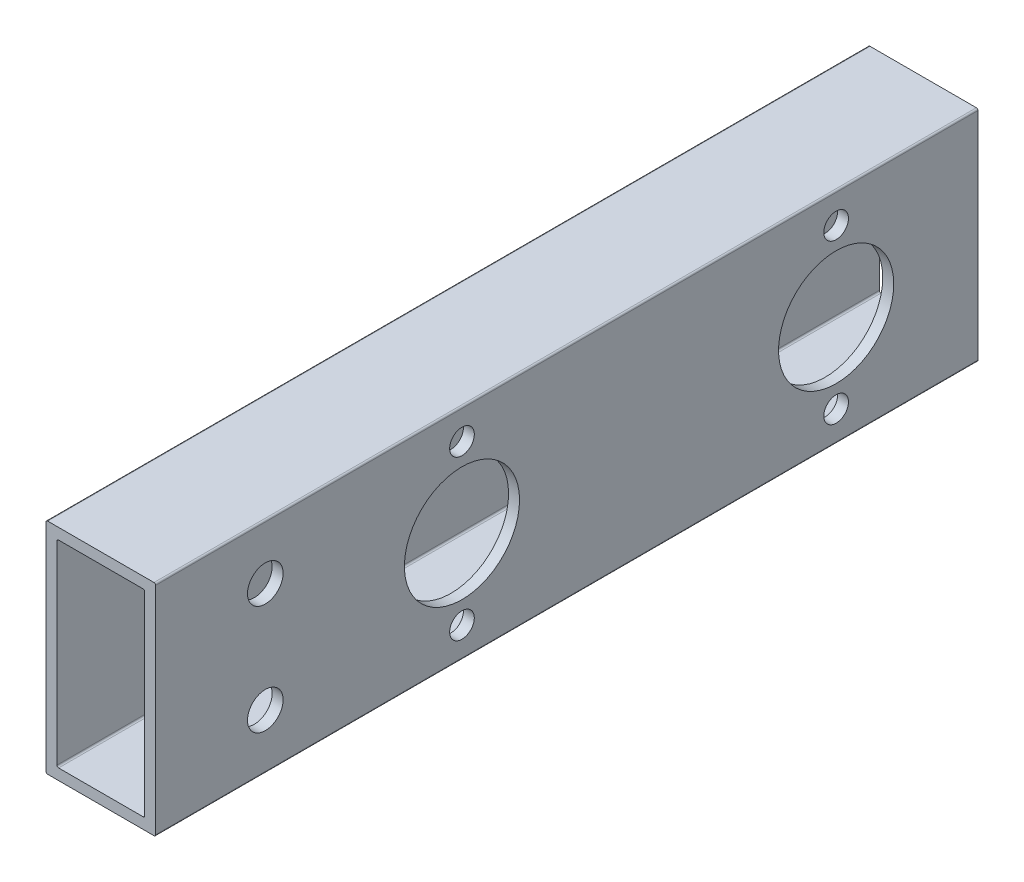
SolidWorks part; units mm, degrees
ref_plane "正面" through (0, 0, 0) normal (0, 0, 1) x (1, 0, 0)
ref_plane "平面" through (0, 0, 0) normal (0, 1, 0) x (1, 0, 0)
ref_plane "右側面" through (0, 0, 0) normal (1, 0, 0) x (0, 0, -1)
ref_plane "平面1" through (0, 0, 0) normal (0, 0, 1) x (1, 0, 0)
sketch "ｽｹｯﾁ1" plane through (0, 0, 0) normal (0, 0, 1) x (1, 0, 0)
  line L0 (0.3, 0) -> (19.7, 0)
  line L1 (20, 0.3) -> (20, 39.7)
  line L2 (19.7, 40) -> (0.3, 40)
  line L3 (0, 39.7) -> (0, 0.3)
  line L4 (2.3, 2) -> (17.7, 2)
  line L5 (18, 2.3) -> (18, 37.7)
  line L6 (17.7, 38) -> (2.3, 38)
  line L7 (2, 37.7) -> (2, 2.3)
  arc A0 (0, 0.3) -> (0.3, 0) centre (0.3, 0.3) ccw
  arc A1 (19.7, 0) -> (20, 0.3) centre (19.7, 0.3) ccw
  arc A2 (20, 39.7) -> (19.7, 40) centre (19.7, 39.7) ccw
  arc A3 (0.3, 40) -> (0, 39.7) centre (0.3, 39.7) ccw
  arc A4 (2, 2.3) -> (2.3, 2) centre (2.3, 2.3) ccw
  arc A5 (17.7, 2) -> (18, 2.3) centre (17.7, 2.3) ccw
  arc A6 (18, 37.7) -> (17.7, 38) centre (17.7, 37.7) ccw
  arc A7 (2.3, 38) -> (2, 37.7) centre (2.3, 37.7) ccw
extrude "ﾎﾞｽ - 押し出し1" add sketch "ｽｹｯﾁ1" against normal blind 150
sketch "ｽｹｯﾁ2" plane through (0, 0, 0) normal (-1, 0, 0) x (0, 0, 1)
  circle A0 centre (-20, 30) radius 3.25
  circle A1 centre (-20, 10) radius 3.25
extrude "ｶｯﾄ - 押し出し1" cut sketch "ｽｹｯﾁ2" against normal through all
sketch "ｽｹｯﾁ3" plane through (20, 0, 0) normal (1, 0, 0) x (0, 0, -1)
  line L0 (150, 20) -> (124.125, 20) construction
  line L1 (150, 0.3) -> (150, 39.7) construction
  circle A0 centre (124.125, 20) radius 10.5
  dimension "D1" = 21
extrude "ｶｯﾄ - 押し出し2" cut sketch "ｽｹｯﾁ3" against normal through all
sketch "ｽｹｯﾁ4" plane through (20, 0, 0) normal (1, 0, 0) x (0, 0, -1)
  line L0 (30, 20) -> (55.875, 20) construction
  line L1 (30, 38) -> (30, 2) construction
  circle A0 centre (55.875, 20) radius 10.5
  dimension "D1" = 21
extrude "ｶｯﾄ - 押し出し3" cut sketch "ｽｹｯﾁ4" against normal through all
sketch "ｽｹｯﾁ5" plane through (20, 0, 0) normal (1, 0, 0) x (0, 0, -1)
  circle A0 centre (55.875, 34.5) radius 2.25
  circle A1 centre (55.875, 5.5) radius 2.25
  circle A2 centre (124.125, 5.5) radius 2.25
  circle A3 centre (124.125, 34.5) radius 2.25
  point P4 (55.875, 20.4299)
  point P13 (124.125, 20)
  point P16 (55.875, 20.4299)
extrude "ｶｯﾄ - 押し出し4" cut sketch "ｽｹｯﾁ5" against normal blind 10 contours A2 region at (20, 5.5, -124.125)
extrude "ｶｯﾄ - 押し出し5" cut sketch "ｽｹｯﾁ5<4>" against normal blind 10
sketch "ｽｹｯﾁ5<4>" plane through (20, 0, 0) normal (1, 0, 0) x (0, 0, -1) same geometry as "ｽｹｯﾁ5"
